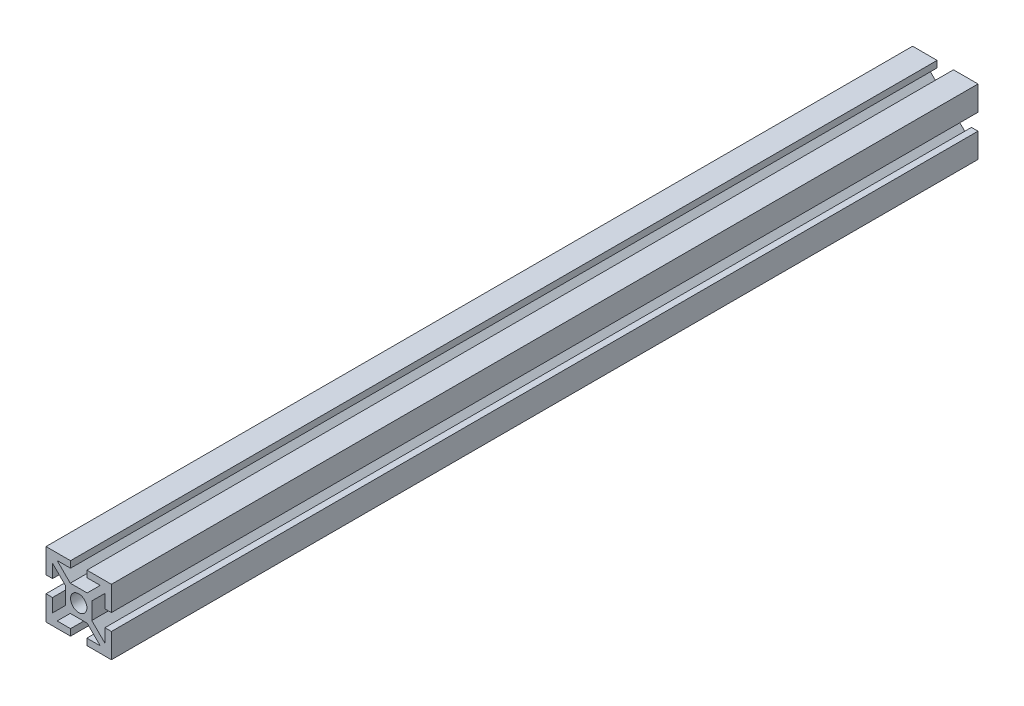
SolidWorks part; units mm, degrees
ref_plane "Front Plane" through (0, 0, 0) normal (0, 0, 1) x (1, 0, 0)
ref_plane "Top Plane" through (0, 0, 0) normal (0, 1, 0) x (1, 0, 0)
ref_plane "Right Plane" through (0, 0, 0) normal (1, 0, 0) x (0, 0, -1)
sketch "Sketch1" plane through (0, 0, 0) normal (0, 0, 1) x (1, 0, 0)
  line L0 (0, 4) -> (0, -4) construction
  line L1 (-2.5858, 4) -> (2.5858, 4)
  line L2 (-4, 2.5858) -> (-4, -2.5858)
  line L5 (-10, 10) -> (0, 0) construction
  line L6 (0, 10) -> (0, 4) construction
  line L7 (-4, 2.5858) -> (-8, 6.5858)
  line L8 (-6.5858, 8) -> (-2.5, 8)
  line L9 (-2.5, 8) -> (-2.5, 10)
  line L10 (-2.5, 10) -> (-10, 10)
  line L11 (-10, 10) -> (-10, 2.5)
  line L12 (-10, 2.5) -> (-8, 2.5)
  line L13 (-8, 2.5) -> (-8, 6.5858)
  line L14 (-4, 0) -> (4, 0) construction
  line L15 (-4, 0) -> (-10, 0) construction
  line L16 (-2.5858, 4) -> (-6.5858, 8)
  line L17 (-10, -10) -> (0, 0) construction
  line L18 (-2.5858, -4) -> (-6.5858, -8)
  line L19 (-8, -2.5) -> (-8, -6.5858)
  line L20 (-10, -2.5) -> (-8, -2.5)
  line L21 (-10, -10) -> (-10, -2.5)
  line L22 (-2.5, -10) -> (-10, -10)
  line L23 (-2.5, -8) -> (-2.5, -10)
  line L24 (-6.5858, -8) -> (-2.5, -8)
  line L25 (-4, -2.5858) -> (-8, -6.5858)
  line L26 (-2.5858, -4) -> (2.5858, -4)
  line L27 (10, -10) -> (0, 0) construction
  line L28 (4, 0) -> (10, 0) construction
  line L29 (10, 10) -> (0, 0) construction
  line L30 (4, -2.5858) -> (8, -6.5858)
  line L31 (6.5858, -8) -> (2.5, -8)
  line L32 (2.5, -8) -> (2.5, -10)
  line L33 (2.5, -10) -> (10, -10)
  line L34 (10, -10) -> (10, -2.5)
  line L35 (10, -2.5) -> (8, -2.5)
  line L36 (8, -2.5) -> (8, -6.5858)
  line L37 (2.5858, -4) -> (6.5858, -8)
  line L38 (2.5858, 4) -> (6.5858, 8)
  line L39 (8, 2.5) -> (8, 6.5858)
  line L40 (10, 2.5) -> (8, 2.5)
  line L41 (10, 10) -> (10, 2.5)
  line L42 (2.5, 10) -> (10, 10)
  line L43 (2.5, 8) -> (2.5, 10)
  line L44 (6.5858, 8) -> (2.5, 8)
  line L45 (4, 2.5858) -> (8, 6.5858)
  line L46 (4, 2.5858) -> (4, -2.5858)
  point P0 (0, 0)
  dimension "D1" = 10
  dimension "D2" = 4
  dimension "D3" = 2
  dimension "D4" = 10
  dimension "D5" = 2
  dimension "D6" = 2.5
  dimension "D7" = 2.5
  dimension "D8" = 4
  dimension "D9" = 1
  dimension "D10" = 1
extrude "Boss-Extrude1" add sketch "Sketch1" along normal mid plane 265
sketch "Sketch2" plane through (0, 0, 0) normal (0, 0, 1) x (1, 0, 0)
  circle A0 centre (0, 0) radius 2.5
  dimension "D1" = 5
extrude "Cut-Extrude3" cut sketch "Sketch2" along direction (0, 0, -1) on the side against the normal blind 132.5 and the other way blind 132.5
